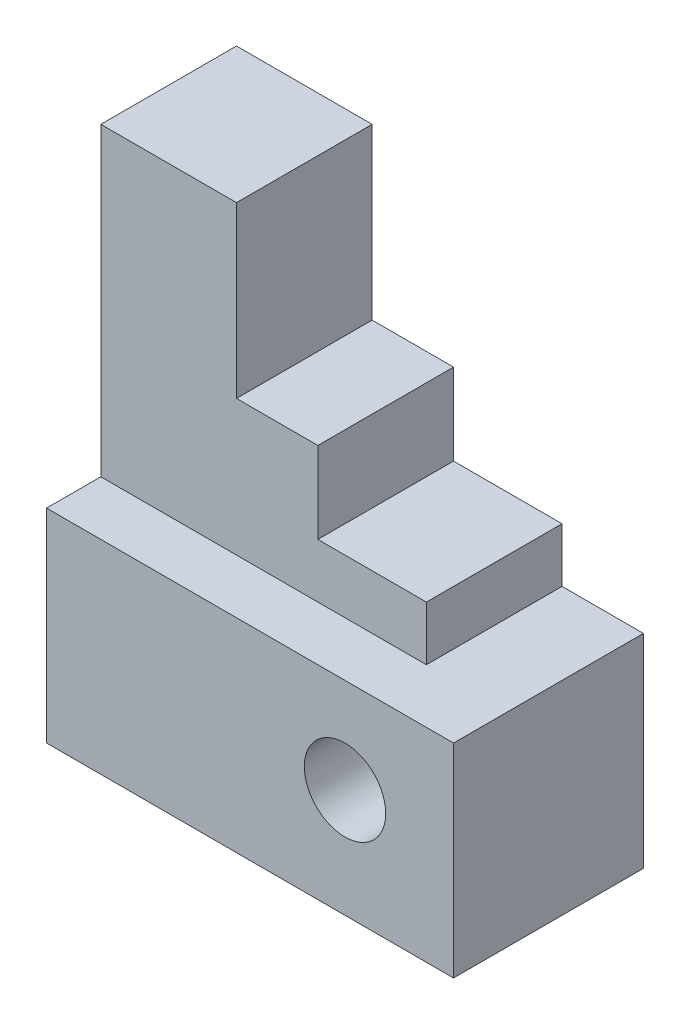
SolidWorks part; units mm, degrees
material "Aluminum Bronze"
ref_plane "Front Plane" through (0, 0, 0) normal (0, 0, 1) x (1, 0, 0)
ref_plane "Top Plane" through (0, 0, 0) normal (0, 1, 0) x (1, 0, 0)
ref_plane "Right Plane" through (0, 0, 0) normal (1, 0, 0) x (0, 0, -1)
sketch "Sketch3" plane through (0, 0, 0) normal (0, 0, 1) x (1, 0, 0)
  line L0 (0, 0) -> (0, 75)
  line L1 (0, 75) -> (20, 75)
  line L2 (20, 75) -> (20, 50)
  line L4 (48, 30) -> (60, 30)
  line L5 (60, 30) -> (60, 0)
  line L6 (60, 0) -> (0, 0)
  line L7 (48, 30) -> (0, 30)
  line L8 (20, 50) -> (32, 50)
  line L9 (32, 50) -> (32, 38)
  line L10 (32, 38) -> (48, 38)
  line L11 (48, 38) -> (48, 30)
  circle A0 centre (44, 16) radius 6
  point P14 (32, 44)
  dimension "D2" = 12
  dimension "D1" = 16
  dimension "D3" = 16
  dimension "D4" = 60
  dimension "D5" = 12
  dimension "D6" = 20
  dimension "D7" = 75
  dimension "D8" = 30
  dimension "D9" = 20
  dimension "D10" = 12
  dimension "D11" = 12
extrude "Boss-Extrude2" add sketch "Sketch3" along normal blind 20 contours L7 L2 L1 L0 | L4 L7 L0 L6 L5 A0 region at (29.0614, 14.933, 0) region at (16.0568, 48.2666, 0)
extrude "Boss-Extrude3" add sketch "Sketch3<3>" along normal blind 8 from surface contours L4 L7 L0 L6 L5 A0 region at (29.0614, 14.933, 0) starting at face at (32, 38.6, 20)
sketch "Sketch3<3>" plane through (0, 0, 0) normal (0, 0, 1) x (1, 0, 0) same geometry as "Sketch3"
